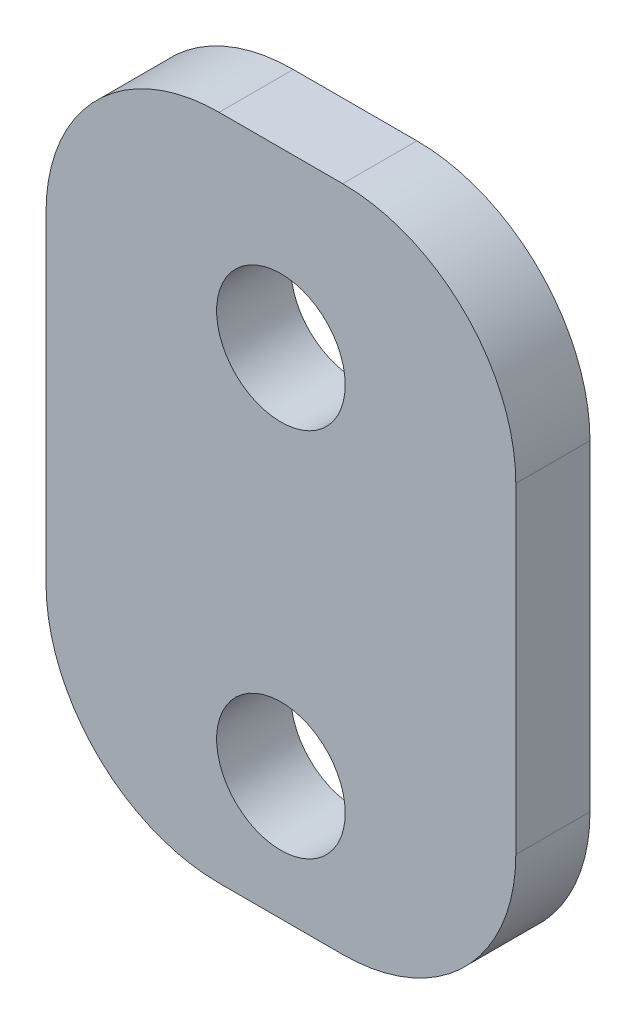
SolidWorks part; units mm, degrees
ref_plane "Front Plane" through (0, 0, 0) normal (0, 0, 1) x (1, 0, 0)
ref_plane "Top Plane" through (0, 0, 0) normal (0, 1, 0) x (1, 0, 0)
ref_plane "Right Plane" through (0, 0, 0) normal (1, 0, 0) x (0, 0, -1)
sketch "Sketch1" plane through (0, 0, 0) normal (0, 0, 1) x (1, 0, 0)
  line L8 (-9.5, -13) -> (-9.5, -33)
  line L9 (-2.5, -40) -> (2.5, -40)
  line L10 (9.5, -33) -> (9.5, -13)
  line L11 (9.5, -13) -> (-9.5, -13)
  circle A1 centre (0, -35) radius 2.6
  arc A4 (-9.5, -33) -> (-2.5, -40) centre (-2.5, -33) ccw
  arc A5 (2.5, -40) -> (9.5, -33) centre (2.5, -33) ccw
  circle A7 centre (0, -20) radius 2.6
  dimension "D1" = 20
base flange "Base-Flange1" sketch "Sketch1" thickness 3 reverse thickness direction no parameters "D1"=3
fillet "Fillet1" radius 7 2 edges at (-9.5, -13, -1.5) (9.5, -13, -1.5)
sketch "Bend-Lines1" [suppressed] plane through (0, 0, 0) normal (0, 1, 0) x (1, 0, 0)
sketch "Bounding-Box1" [suppressed] plane through (0, 0, 0) normal (0, 1, 0) x (1, 0, 0)
sheet metal parameters "Sheet-Metal1" thickness 3 parameters "D1"=3
flat pattern "Flat-Pattern1" [suppressed]
sketch "Bend-Lines2" plane through (0, 0, 0) normal (0, 1, 0) x (1, 0, 0)
sketch3d "Bounding-Box2" [suppressed]
  line L0 (12, -7, 0) -> (12, 20, 0) construction
  line L1 (-7, -7, 0) -> (-7, 20, 0) construction
  line L2 (12, -7, 0) -> (-7, -7, 0) construction
  line L3 (12, 20, 0) -> (-7, 20, 0) construction
